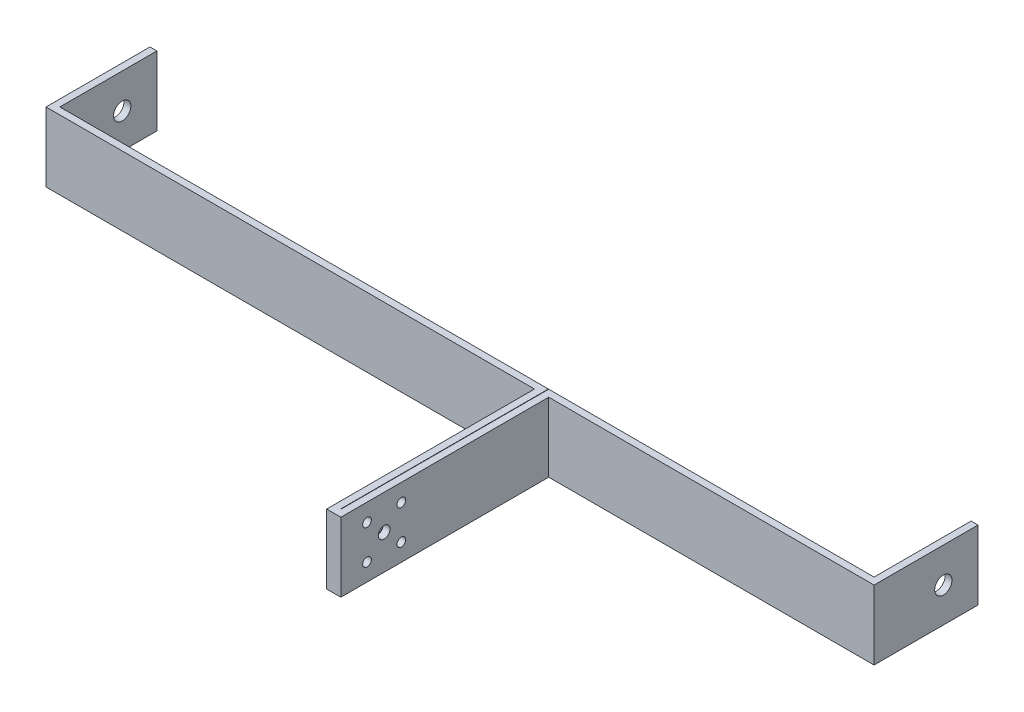
SolidWorks part; units mm, degrees
ref_plane "Front Plane" through (0, 0, 0) normal (0, 0, 1) x (1, 0, 0)
ref_plane "Top Plane" through (0, 0, 0) normal (0, 1, 0) x (1, 0, 0)
ref_plane "Right Plane" through (0, 0, 0) normal (1, 0, 0) x (0, 0, -1)
sketch "Sketch1" plane through (0, 0, 0) normal (0, 1, 0) x (1, 0, 0)
  line L0 (-117.5, 0) -> (117.5, 0) construction
  line L1 (117.5, -175) -> (-117.5, -175)
  line L2 (117.5, -175) -> (117.5, 175)
  line L3 (117.5, 175) -> (-117.5, 175)
  line L4 (-117.5, -175) -> (-117.5, 175)
  line L5 (117.5, -175) -> (-117.5, 175) construction
  line L6 (117.5, 175) -> (-117.5, -175) construction
  line L7 (-117.5, 10) -> (-119.5, 10)
  line L8 (-119.5, 10) -> (-119.5, -20)
  line L9 (-119.5, -20) -> (21.5, -20)
  line L10 (-117.5, 10) -> (-117.5, -18)
  line L11 (0, 0) -> (0, -20)
  line L12 (0, 0) -> (0, 21.8904) construction
  line L13 (-117.5, -18) -> (23.5, -18)
  line L14 (117.5, 10) -> (117.5, -18)
  line L15 (117.5, 10) -> (119.5, 10)
  line L16 (119.5, 10) -> (119.5, -20)
  line L17 (0, -20) -> (0, -53.7476) construction
  line L18 (21.5, -20) -> (21.5, -80)
  line L19 (21.5, -80) -> (25.6, -80)
  line L20 (25.6, -80) -> (25.6, -20)
  line L21 (23.5, -18) -> (23.5, -78)
  line L22 (23.5, -78) -> (23.6, -78)
  line L23 (23.6, -78) -> (23.6, -18)
  line L24 (21.5, -18) -> (21.5, -80) construction
  line L25 (25.6, -80) -> (25.6, -18) construction
  line L26 (25.6, -20) -> (119.5, -20)
  line L27 (23.6, -18) -> (117.5, -18)
  point P0 (0, 0)
  point P18 (0, -18)
  dimension "D1" = 235
  dimension "D2" = 350
  dimension "D3" = 2
  dimension "D4" = 30
  dimension "D5" = 2
  dimension "D6" = 21.5
  dimension "D7" = 4.1
  dimension "D9" = 60
  dimension "D8" = 2
extrude "Boss-Extrude1" add sketch "Sketch1" along normal blind 10 and the other way blind 10 contours L13 L11 L9 L2 | L16 L15 L2 L9 | L13 L4 L9 L11 | L8 L9 L4 L7 region at (71.55, 0, 18.6715) region at (118.5, 0, 5) region at (-118.5, 0, 5) region at (-58.75, 0, 19)
sketch "Sketch2" plane through (-119.5, 0, 0) normal (-1, 0, 0) x (0, 0, 1)
  circle A0 centre (0, 0) radius 2.5
  dimension "D1" = 5
extrude "Cut-Extrude1" cut sketch "Sketch2" against normal blind 285
sketch "Sketch3" plane through (25.6, 0, 0) normal (1, 0, 0) x (0, 0, -1)
  line L0 (-80, 10) -> (-80, -10) construction
  line L1 (-80, 0) -> (-67.5, 0) construction
  circle A0 centre (-67.5, 0) radius 1.7
  circle A1 centre (-72.4497, -4.9497) radius 1.25
  circle A2 centre (-72.4497, 4.9497) radius 1.25
  circle A3 centre (-62.5503, 4.9497) radius 1.25
  circle A4 centre (-62.5503, -4.9497) radius 1.25
  point P19 (-67.5, 0)
  dimension "D2" = 4
  dimension "D1" = 12.5
  dimension "D3" = 7
extrude "Cut-Extrude2" cut sketch "Sketch3" against normal blind 285
